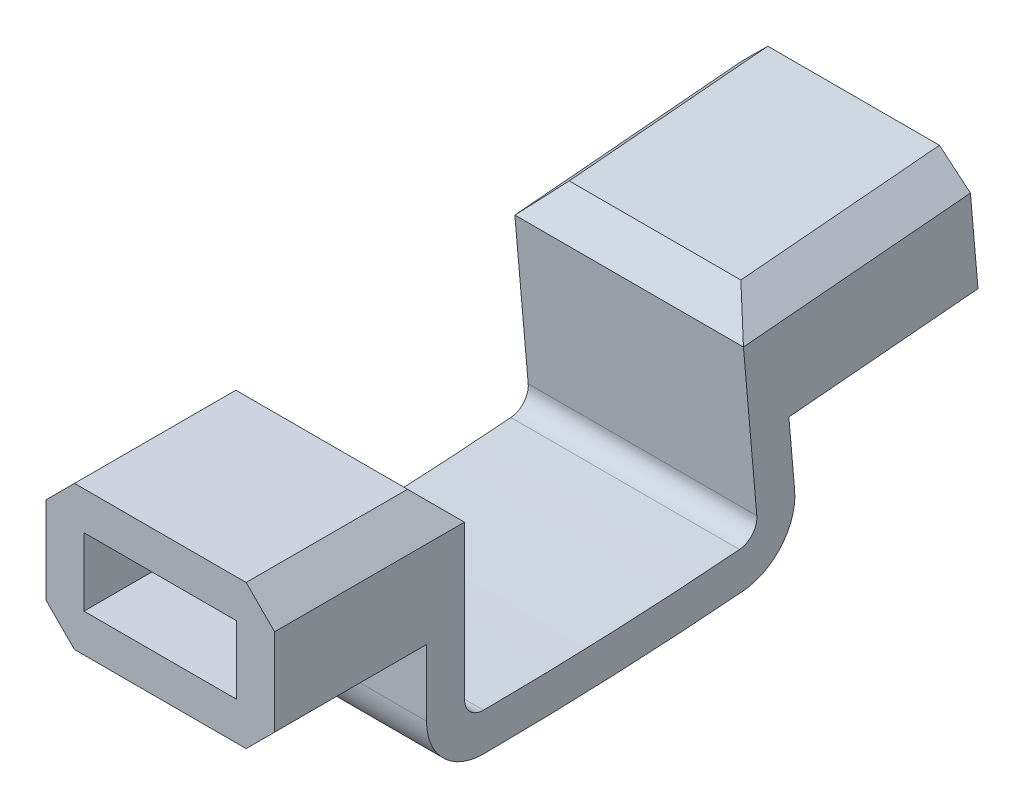
SolidWorks part; units mm, degrees
ref_plane "Front Plane" through (0, 0, 0) normal (0, 0, 1) x (1, 0, 0)
ref_plane "Top Plane" through (0, 0, 0) normal (0, 1, 0) x (1, 0, 0)
ref_plane "Right Plane" through (0, 0, 0) normal (1, 0, 0) x (0, 0, -1)
other "Configuration Table"
sketch "Sketch1" plane through (0, 0, 0) normal (0, 0, 1) x (1, 0, 0)
  line L1 (4.02, -1.79) -> (-4.02, -1.79)
  line L2 (4.02, -1.79) -> (4.02, 1.79)
  line L3 (4.02, 1.79) -> (-4.02, 1.79)
  line L4 (-4.02, -1.79) -> (-4.02, 1.79)
  line L5 (0, 1.79) -> (0, -1.79) construction
  line L6 (4.02, 0) -> (-4.02, 0) construction
  line L7 (-6.02, 3.79) -> (6.02, 3.79)
  line L8 (-6.02, 3.79) -> (-6.02, -3.79)
  line L9 (-6.02, -3.79) -> (6.02, -3.79)
  line L10 (6.02, 3.79) -> (6.02, -3.79)
  line L11 (0, -3.79) -> (0, 3.79) construction
  line L12 (-6.02, 0) -> (6.02, 0) construction
  point P0 (0, 0)
  point P4 (0, 0)
  dimension "D1" = 3.58
  dimension "D2" = 8.04
  dimension "D3" = 2
  dimension "D4" = 2
extrude "Boss-Extrude1" add sketch "Sketch1" along normal blind 8
extrude "Boss-Extrude2" add sketch "Sketch1<2>" against normal blind 2 contours L4 L1 L2 L3 | L10 L7 L8 L9 L1 L4 L3 L2 region at (0, 0, 0) region at (0, 3.6477, 0)
sketch "Sketch1<2>" plane through (0, 0, 0) normal (0, 0, 1) x (1, 0, 0) same geometry as "Sketch1"
sketch "Sketch3" plane through (6.02, 9.81, 0) normal (1, 0, 0) x (0, -1, 0)
  line L0 (13.6, 2) -> (15.5972, 2)
  line L2 (14.9249, 17.3978) -> (12.9353, 17.2238)
  line L3 (13.6, -8) -> (13.6, 2) construction
  arc A1 (16.5972, 3.0057) -> (16.0087, 16.4832) centre (-161.0733, 2) ccw
  arc A3 (12.9353, 17.2238) -> (13.6, 2) centre (-161.0733, 2) cw construction
  arc A4 (15.5972, 2) -> (16.5972, 3.0057) centre (15.5972, 3) ccw
  arc A5 (16.0087, 16.4832) -> (14.9249, 17.3978) centre (15.012, 16.4017) ccw
  point P4 (16.6, 2)
  point P12 (15.9239, 17.4852)
  dimension "D1" = 3
  dimension "D3" = 1
  dimension "D4" = 5
  dimension "D2" = 15.5
extrude "Extrude-Thin1" add sketch "Sketch3" along normal up to surface (-12.04 mm away) thin contours L0 A4 A1 A5 L2 up to face at (-6.02, 0, 3) thin type one direction wall 2
sketch "Sketch5" plane through (0, -2.1049, -19.1421) normal (0, -0.0872, 0.9962) x (1, 0, 0)
  line L0 (-6.02, -0.8493) -> (-6.02, -2.8465) construction
  line L1 (4.02, 1.1507) -> (-4.02, 1.1507)
  line L2 (4.02, 1.1507) -> (4.02, 4.7307)
  line L3 (4.02, 4.7307) -> (-4.02, 4.7307)
  line L4 (-4.02, 1.1507) -> (-4.02, 4.7307)
  line L5 (0, 4.7307) -> (0, 1.1507) construction
  line L6 (4.02, 2.9407) -> (-4.02, 2.9407) construction
  line L7 (-6.02, 6.7307) -> (6.02, 6.7307)
  line L8 (-6.02, 6.7307) -> (-6.02, -0.8493)
  line L9 (-6.02, -0.8493) -> (6.02, -0.8493)
  line L10 (6.02, 6.7307) -> (6.02, -0.8493)
  line L11 (0, -0.8493) -> (0, 6.7307) construction
  line L12 (-6.02, 2.9407) -> (6.02, 2.9407) construction
  point P0 (0, 2.9407)
  point P4 (0, 2.9407)
  dimension "D1" = 3.58
  dimension "D2" = 8.04
  dimension "D3" = 2
  dimension "D4" = 2
extrude "Boss-Extrude4" add sketch "Sketch5" against normal blind 10
extrude "Boss-Extrude5" add sketch "Sketch5<4>" along normal blind 2 contours L8 L7 L10 L9
sketch "Sketch5<4>" plane through (0, -2.1049, -19.1421) normal (0, -0.0872, 0.9962) x (1, 0, 0) same geometry as "Sketch5"
chamfer "Chamfer1" distance 1.5 angle 45 10 edges at (6.02, 4.9488, -22.5403) (-6.02, 4.9488, -22.5403) (6.02, 3.79, 3) (6.02, -3.79, 4) (-6.02, -3.79, 4) (-6.02, 3.79, 3) (0, 3.79, -2) (0, 4.4258, -16.5631) (6.02, -2.5152, -24.1971) (-6.02, -2.5152, -24.1971)
equation "\"LF\" = 0.04mm"
equation "\"TF\" = 0.02mm"
equation "\"AngLF\"= 0.5"
equation "\"AngTF\"= 0.3"
equation "\"D2@Sketch1\"=8+2*\"TF\""
equation "\"D1@Sketch1\"=3.5+2*\"LF\""
